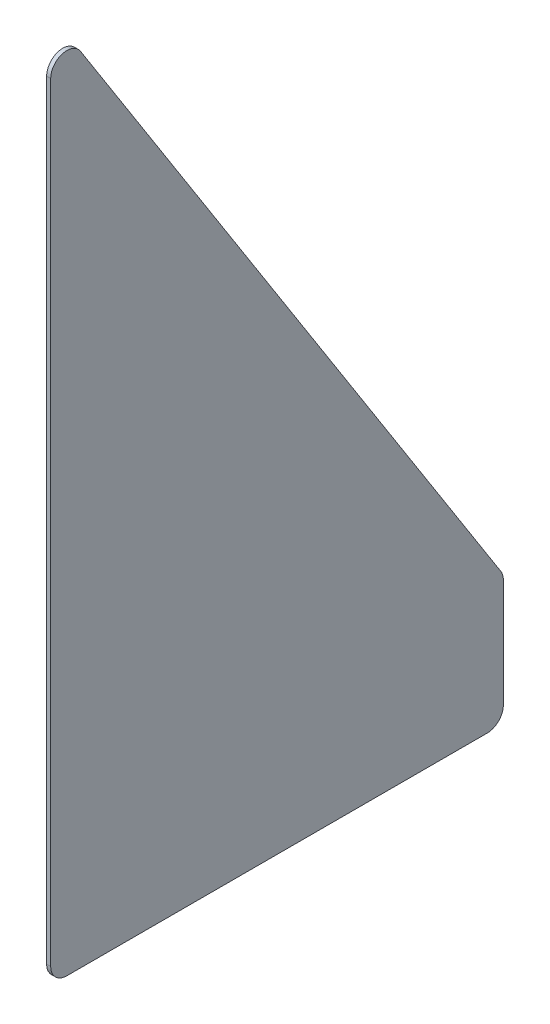
SolidWorks part; units mm, degrees
ref_plane "Front Plane" through (0, 0, 0) normal (0, 0, 1) x (1, 0, 0)
ref_plane "Top Plane" through (0, 0, 0) normal (0, 1, 0) x (1, 0, 0)
ref_plane "Right Plane" through (0, 0, 0) normal (1, 0, 0) x (0, 0, -1)
sketch "Sketch1" plane through (0, 0, 0) normal (0, 1, 0) x (1, 0, 0)
  line L0 (0, 0) -> (0, 177.8)
  line L1 (0, 177.8) -> (1.5875, 177.8)
  line L2 (1.5875, 177.8) -> (1.5875, 0)
  line L5 (1.5875, 0) -> (0, 0)
  point P3 (0, 0)
  dimension "D2" = 177.8
  dimension "D4" = 1.5875
extrude "Boss-Extrude1" add sketch "Sketch1" along normal blind 330.2
sketch "Sketch2" plane through (0, 0, 0) normal (-1, 0, 0) x (0, 0, 1)
  line L0 (-177.8, 50.8) -> (0, 330.2)
  line L1 (0, 330.2) -> (-177.8, 330.2)
  line L2 (-177.8, 330.2) -> (-177.8, 50.8)
  line L4 (-177.8, 330.2) -> (-177.8, 0) construction
  line L5 (-177.8, 330.2) -> (0, 330.2) construction
  line L6 (0, 330.2) -> (0, 0) construction
  point P2 (0, 0)
  dimension "D2" = 50.8
extrude "Cut-Extrude1" cut sketch "Sketch2" against normal up to surface (1.5875 mm away) up to face at (1.5875, 165.1, -88.9)
fillet "Fillet1" radius 6.35 4 edges at (0.7937, 0, -177.8) (0.7937, 0, 0) (0.7937, 330.2, 0) (0.7937, 50.8, -177.8)
